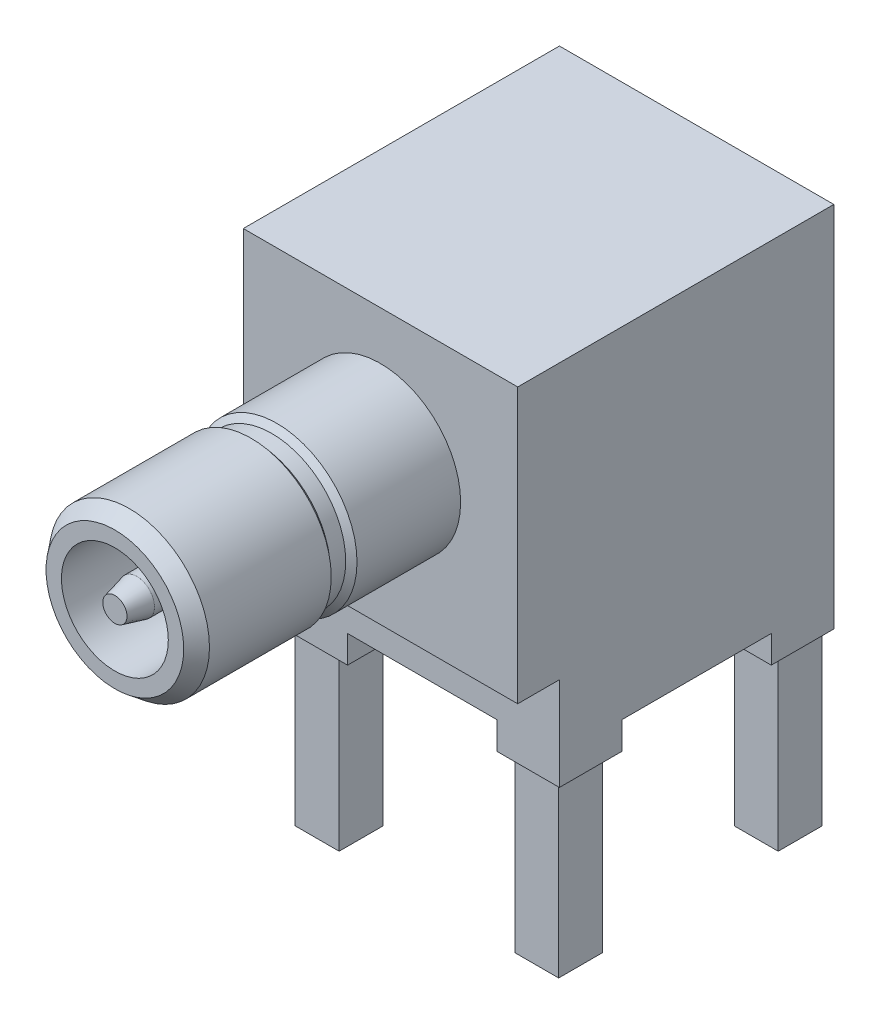
SolidWorks part; units mm, degrees
ref_plane "Front" through (0, 0, 0) normal (0, 0, 1) x (1, 0, 0)
ref_plane "Top" through (0, 0, 0) normal (0, 1, 0) x (1, 0, 0)
ref_plane "Right" through (0, 0, 0) normal (1, 0, 0) x (0, 0, -1)
sketch "Sketch1" plane through (0, 0, 0) normal (0, 1, 0) x (1, 0, 0)
  line L1 (0, 0) -> (6.35, 0)
  line L2 (0, 0) -> (0, 6.35)
  line L3 (0, 6.35) -> (6.35, 6.35)
  line L4 (6.35, 0) -> (6.35, 6.35)
  dimension "D1" = 6.35
  dimension "D2" = 6.35
extrude "Extrude1" add sketch "Sketch1" along normal blind 7.874
sketch "Sketch2" plane through (0, 0, 0) normal (0, -1, 0) x (1, 0, 0)
  line L0 (6.35, -3.175) -> (0, -3.175) construction
  line L1 (6.35, 0) -> (4.9022, 0)
  line L2 (6.35, 0) -> (6.35, -1.4478)
  line L3 (6.35, -1.4478) -> (4.9022, -1.4478)
  line L4 (4.9022, 0) -> (4.9022, -1.4478)
  line L5 (6.35, 0) -> (6.35, -6.35) construction
  line L6 (0, -6.35) -> (0, 0) construction
  line L7 (3.175, -6.35) -> (3.175, 0) construction
  line L8 (6.35, -6.35) -> (0, -6.35) construction
  line L9 (0, 0) -> (6.35, 0) construction
  line L10 (4.9022, -6.35) -> (4.9022, -4.9022)
  line L11 (6.35, -4.9022) -> (4.9022, -4.9022)
  line L12 (6.35, -6.35) -> (6.35, -4.9022)
  line L13 (6.35, -6.35) -> (4.9022, -6.35)
  line L14 (0, -6.35) -> (1.4478, -6.35)
  line L15 (0, -6.35) -> (0, -4.9022)
  line L16 (0, -4.9022) -> (1.4478, -4.9022)
  line L17 (1.4478, -6.35) -> (1.4478, -4.9022)
  line L18 (1.4478, 0) -> (1.4478, -1.4478)
  line L19 (0, -1.4478) -> (1.4478, -1.4478)
  line L20 (0, 0) -> (0, -1.4478)
  line L21 (0, 0) -> (1.4478, 0)
  dimension "D1" = 1.7272
  dimension "D2" = 1.7272
extrude "Extrude2" add sketch "Sketch2" along normal blind 0.635
sketch "Sketch3" plane through (0, -0.635, 0) normal (0, -1, 0) x (1, 0, 0)
  line L0 (6.35, 0) -> (0, 0) construction
  line L1 (3.175, 0) -> (3.175, -6.3153) construction
  line L2 (3.175, -3.1576) -> (9.0771, -3.1576) construction
  line L3 (5.715, -1.1256) -> (5.715, -0.1096) construction
  line L4 (6.223, -0.1096) -> (5.207, -0.1096)
  line L5 (6.223, -0.1096) -> (6.223, -1.1256)
  line L6 (6.223, -1.1256) -> (5.207, -1.1256)
  line L7 (5.207, -0.1096) -> (5.207, -1.1256)
  line L8 (6.223, -0.6176) -> (5.207, -0.6176) construction
  line L9 (6.223, -6.2056) -> (5.207, -6.2056)
  line L10 (5.207, -6.2056) -> (5.207, -5.1896)
  line L11 (6.223, -5.1896) -> (5.207, -5.1896)
  line L12 (6.223, -6.2056) -> (6.223, -5.1896)
  line L13 (0.127, -6.2056) -> (0.127, -5.1896)
  line L14 (0.127, -5.1896) -> (1.143, -5.1896)
  line L15 (1.143, -6.2056) -> (1.143, -5.1896)
  line L16 (0.127, -6.2056) -> (1.143, -6.2056)
  line L17 (0.127, -0.1096) -> (0.127, -1.1256)
  line L18 (0.127, -0.1096) -> (1.143, -0.1096)
  line L19 (1.143, -0.1096) -> (1.143, -1.1256)
  line L20 (0.127, -1.1256) -> (1.143, -1.1256)
  dimension "D1" = 1.016
  dimension "D2" = 1.016
  dimension "D3" = 5.08
  dimension "D4" = 5.08
extrude "Extrude3" add sketch "Sketch3" along normal blind 3.937
sketch "Sketch4" plane through (0, 0, 0) normal (0, -1, 0) x (1, 0, 0)
  line L0 (3.175, 0) -> (3.175, -6.35) construction
  line L1 (1.4478, 0) -> (4.9022, 0) construction
  line L2 (4.9022, -6.35) -> (1.4478, -6.35) construction
  line L3 (6.35, -3.175) -> (0, -3.175) construction
  line L4 (6.35, -1.4478) -> (6.35, -4.9022) construction
  line L5 (0, -4.9022) -> (0, -1.4478) construction
  circle A0 centre (3.175, -3.175) radius 1.6936
extrude "Cut-Extrude1" cut sketch "Sketch4" against normal blind 0.254
sketch "Sketch5" plane through (0, 0.254, 0) normal (0, -1, 0) x (1, 0, 0)
  circle A0 centre (3.175, -3.175) radius 0.4826
  dimension "D1" = 0.9652
extrude "Extrude4" add sketch "Sketch5" along normal up to surface (4.826 mm away) up to face at (5.715, -4.572, -0.6176)
sketch "Sketch6" plane through (0, 0, 0) normal (0, 0, 1) x (1, 0, 0)
  line L0 (3.175, 7.874) -> (3.175, 1.7909) construction
  line L1 (0, 7.874) -> (6.35, 7.874) construction
  line L2 (-0.9192, 4.9022) -> (7.9319, 4.9022) construction
  line L3 (6.223, -0.635) -> (5.207, -0.635) construction
  line L4 (6.35, 7.874) -> (6.35, -0.635) construction
  line L5 (0, 7.874) -> (6.35, 7.874)
  line L6 (0, 7.874) -> (0, 1.524)
  line L7 (0, 1.524) -> (6.35, 1.524)
  line L8 (6.35, 7.874) -> (6.35, 1.524)
  dimension "D2" = 6.35
  dimension "D1" = 5.5372
extrude "Extrude5" add sketch "Sketch6" along normal blind 0.9652
sketch "Sketch7" plane through (0, 0, 0.9652) normal (0, 0, 1) x (1, 0, 0)
  line L0 (3.175, 7.874) -> (3.175, 1.7909) construction
  line L1 (-0.9192, 4.9022) -> (7.9319, 4.9022) construction
  line L2 (3.175, 7.874) -> (3.175, 1.7909) construction
  line L3 (-0.9192, 4.9022) -> (7.9319, 4.9022) construction
  circle A0 centre (3.175, 4.9022) radius 1.8542
  dimension "D1" = 3.7084
extrude "Extrude6" add sketch "Sketch7" along normal blind 6.1468
ref_axis "Axis1" through (3.175, 4.9022, 7.112) along (0, 0, -1)
ref_plane "Plane1" through (0, 4.9022, 0) normal (0, 1, 0) x (-1, 0, 0)
sketch "Sketch8" plane through (0, 4.9022, 0) normal (0, 1, 0) x (-1, 0, 0)
  line L0 (-4.7678, 7.112) -> (-5.0292, 6.7771)
  line L1 (-1.3208, 7.112) -> (-5.0292, 7.112) construction
  line L2 (-5.0292, 7.112) -> (-5.0292, 0.9652) construction
  line L3 (-5.0292, 6.7771) -> (-5.0292, 3.9595)
  line L4 (-5.0292, 3.9595) -> (-4.8843, 3.8357)
  line L5 (-4.8843, 3.4795) -> (-4.8843, 3.8357)
  line L6 (-4.8843, 3.4795) -> (-5.0292, 3.3631)
  line L7 (-5.0292, 3.3631) -> (-5.0292, 0.9652)
  line L8 (-5.0292, 0.9652) -> (-5.6506, 0.9652)
  line L9 (-6.35, 0.9652) -> (0, 0.9652) construction
  line L10 (-5.6506, 0.9652) -> (-5.6506, 7.8011)
  line L11 (-5.6506, 7.8011) -> (-4.7678, 7.112)
  line L12 (-4.8843, 3.6576) -> (-5.1823, 3.6576) construction
  line L13 (-3.175, 7.112) -> (-3.175, 1.519) construction
  dimension "D1" = 3.4544
revolve "Cut-Revolve1" cut sketch "Sketch8" angle 360 about L13
sketch "Sketch9" plane through (0, 0, 7.112) normal (0, 0, 1) x (1, 0, 0)
  circle A0 centre (3.175, 4.9022) radius 1.2364
extrude "Cut-Extrude2" cut sketch "Sketch9" against normal blind 5.6581
sketch "Sketch10" plane through (0, 0, 1.4539) normal (0, 0, 1) x (1, 0, 0)
  circle A0 centre (3.175, 4.9022) radius 0.407
extrude "Extrude7" add sketch "Sketch10" along normal blind 5.6581
chamfer "Chamfer1" distance 0.508 angle 14 1 edges at (3.582, 4.9022, 7.112) first distance on face at (3.582, 4.9022, 7.112)
